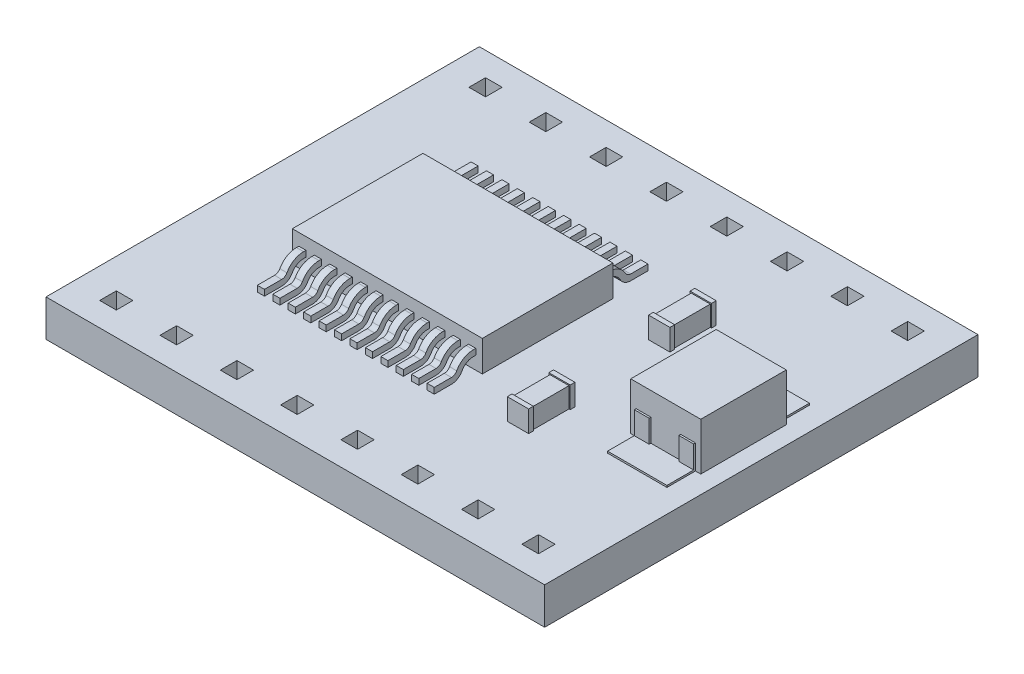
SolidWorks part; units mm, degrees
ref_plane "Спереди" through (0, 0, 0) normal (0, 0, 1) x (1, 0, 0)
ref_plane "Сверху" through (0, 0, 0) normal (0, 1, 0) x (1, 0, 0)
ref_plane "Справа" through (0, 0, 0) normal (1, 0, 0) x (0, 0, -1)
other "Configuration Table"
sketch "Эскиз1" plane through (0, 0, 0) normal (0, 1, 0) x (1, 0, 0)
  line L1 (-10.5, 9.125) -> (10.5, 9.125)
  line L2 (-10.5, 9.125) -> (-10.5, -9.125)
  line L3 (-10.5, -9.125) -> (10.5, -9.125)
  line L4 (10.5, 9.125) -> (10.5, -9.125)
  line L5 (0, -9.125) -> (0, 9.125) construction
  line L6 (-10.5, 0) -> (10.5, 0) construction
  point P0 (0, 0)
  dimension "D1" = 21
  dimension "D2" = 18.25
extrude "Бобышка-Вытянуть1" add sketch "Эскиз1" along normal blind 1.55
sketch "Эскиз2" plane through (0, 1.55, 0) normal (0, 1, 0) x (1, 0, 0)
  line L0 (0, -9.125) -> (0, 9.125) construction
  line L1 (10.5, 9.125) -> (-10.5, 9.125) construction
  line L2 (3.46, 8.125) -> (3.46, 7.425)
  line L3 (0.92, 8.125) -> (1.62, 8.125)
  line L4 (0.92, 8.125) -> (0.92, 7.425)
  line L5 (0.92, 7.425) -> (1.62, 7.425)
  line L6 (1.62, 8.125) -> (1.62, 7.425)
  line L7 (1.27, 7.425) -> (1.27, 8.125) construction
  line L8 (0.92, 7.775) -> (1.62, 7.775) construction
  line L9 (-1.62, 8.125) -> (-0.92, 8.125)
  line L10 (-1.62, 8.125) -> (-1.62, 7.425)
  line L11 (-1.62, 7.425) -> (-0.92, 7.425)
  line L12 (-0.92, 8.125) -> (-0.92, 7.425)
  line L13 (-1.27, 7.425) -> (-1.27, 8.125) construction
  line L14 (-1.62, 7.775) -> (-0.92, 7.775) construction
  line L15 (3.46, 8.125) -> (4.16, 8.125)
  line L16 (4.16, 8.125) -> (4.16, 7.425)
  line L17 (3.46, 7.425) -> (4.16, 7.425)
  line L18 (6, 8.125) -> (6, 7.425)
  line L19 (6, 8.125) -> (6.7, 8.125)
  line L20 (6.7, 8.125) -> (6.7, 7.425)
  line L21 (6, 7.425) -> (6.7, 7.425)
  line L22 (8.54, 8.125) -> (8.54, 7.425)
  line L23 (8.54, 8.125) -> (9.24, 8.125)
  line L24 (9.24, 8.125) -> (9.24, 7.425)
  line L25 (8.54, 7.425) -> (9.24, 7.425)
  line L26 (-8.54, 7.425) -> (-9.24, 7.425)
  line L27 (-9.24, 8.125) -> (-9.24, 7.425)
  line L28 (-8.54, 8.125) -> (-9.24, 8.125)
  line L29 (-8.54, 8.125) -> (-8.54, 7.425)
  line L30 (-6, 7.425) -> (-6.7, 7.425)
  line L31 (-6.7, 8.125) -> (-6.7, 7.425)
  line L32 (-6, 8.125) -> (-6.7, 8.125)
  line L33 (-6, 8.125) -> (-6, 7.425)
  line L34 (-3.46, 7.425) -> (-4.16, 7.425)
  line L35 (-4.16, 8.125) -> (-4.16, 7.425)
  line L36 (-3.46, 8.125) -> (-4.16, 8.125)
  line L37 (-3.46, 8.125) -> (-3.46, 7.425)
  line L38 (0, 0) -> (10.5, 0) construction
  line L39 (10.5, -9.125) -> (10.5, 9.125) construction
  line L40 (-1.62, -7.775) -> (-0.92, -7.775) construction
  line L41 (-1.27, -7.425) -> (-1.27, -8.125) construction
  line L42 (0.92, -7.775) -> (1.62, -7.775) construction
  line L43 (1.27, -7.425) -> (1.27, -8.125) construction
  line L44 (-3.46, -8.125) -> (-3.46, -7.425)
  line L45 (-3.46, -8.125) -> (-4.16, -8.125)
  line L46 (-4.16, -8.125) -> (-4.16, -7.425)
  line L47 (-3.46, -7.425) -> (-4.16, -7.425)
  line L48 (-6, -8.125) -> (-6, -7.425)
  line L49 (-6, -8.125) -> (-6.7, -8.125)
  line L50 (-6.7, -8.125) -> (-6.7, -7.425)
  line L51 (-6, -7.425) -> (-6.7, -7.425)
  line L52 (-8.54, -8.125) -> (-8.54, -7.425)
  line L53 (-8.54, -8.125) -> (-9.24, -8.125)
  line L54 (-9.24, -8.125) -> (-9.24, -7.425)
  line L55 (-8.54, -7.425) -> (-9.24, -7.425)
  line L56 (8.54, -7.425) -> (9.24, -7.425)
  line L57 (9.24, -8.125) -> (9.24, -7.425)
  line L58 (8.54, -8.125) -> (9.24, -8.125)
  line L59 (8.54, -8.125) -> (8.54, -7.425)
  line L60 (6, -7.425) -> (6.7, -7.425)
  line L61 (6.7, -8.125) -> (6.7, -7.425)
  line L62 (6, -8.125) -> (6.7, -8.125)
  line L63 (6, -8.125) -> (6, -7.425)
  line L64 (3.46, -7.425) -> (4.16, -7.425)
  line L65 (4.16, -8.125) -> (4.16, -7.425)
  line L66 (3.46, -8.125) -> (4.16, -8.125)
  line L67 (-0.92, -8.125) -> (-0.92, -7.425)
  line L68 (-1.62, -7.425) -> (-0.92, -7.425)
  line L69 (-1.62, -8.125) -> (-1.62, -7.425)
  line L70 (-1.62, -8.125) -> (-0.92, -8.125)
  line L71 (1.62, -8.125) -> (1.62, -7.425)
  line L72 (0.92, -7.425) -> (1.62, -7.425)
  line L73 (0.92, -8.125) -> (0.92, -7.425)
  line L74 (0.92, -8.125) -> (1.62, -8.125)
  line L75 (3.46, -8.125) -> (3.46, -7.425)
  line L76 (-9.24, 7.775) -> (-8.54, 7.775) construction
  point P5 (1.27, 7.775)
  point P9 (-1.27, 7.775)
  point P86 (-1.27, -7.775)
  point P87 (1.27, -7.775)
  dimension "D1" = 0.7
  dimension "D2" = 2.54
  dimension "D4" = 2.54
  dimension "D5" = 1.35
  dimension "D6" = 0.7
  dimension "D3" = 4
extrude "Вырез-Вытянуть1" cut sketch "Эскиз2" against normal through all
sketch "Эскиз3" plane through (0, 1.55, 0) normal (0, 1, 0) x (1, 0, 0)
  line L0 (-10.5, 9.125) -> (-10.5, -9.125) construction
  line L1 (-6.5, 2.75) -> (1.5, 2.75)
  line L2 (-6.5, 2.75) -> (-6.5, -2.75)
  line L3 (-6.5, -2.75) -> (1.5, -2.75)
  line L4 (1.5, 2.75) -> (1.5, -2.75)
  line L5 (-2.5, -2.75) -> (-2.5, 2.75) construction
  line L6 (-6.5, 0) -> (1.5, 0) construction
  point P0 (-2.5, 0)
  dimension "D1" = 8
  dimension "D2" = 5.5
  dimension "D3" = 4
extrude "Бобышка-Вытянуть2" add sketch "Эскиз3" along normal blind 1.3
sketch "Эскиз4" plane through (0, 1.55, 0) normal (0, 1, 0) x (1, 0, 0)
  line L0 (-2.5, -2.75) -> (-2.5, 2.75) construction
  line L1 (-6.5, -2.75) -> (1.5, -2.75) construction
  line L2 (1.5, 2.75) -> (-6.5, 2.75) construction
  line L3 (-2.325, -2.75) -> (-2.325, -4.5)
  line L4 (-2.325, -4.5) -> (-2.025, -4.5)
  line L5 (-2.025, -4.5) -> (-2.025, -2.75)
  line L6 (-6.5, -2.75) -> (1.5, -2.75) construction
  line L7 (-6.5, 0) -> (1.5, 0) construction
  line L8 (-6.5, 2.75) -> (-6.5, -2.75) construction
  line L9 (1.5, -2.75) -> (1.5, 2.75) construction
  line L10 (-2.325, -2.75) -> (-2.025, -2.75)
  line L11 (-2.325, 2.75) -> (-2.025, 2.75)
  line L12 (-2.025, 4.5) -> (-2.025, 2.75)
  line L13 (-2.325, 4.5) -> (-2.025, 4.5)
  line L14 (-2.325, 2.75) -> (-2.325, 4.5)
  line L15 (-1.675, -2.75) -> (-1.675, -4.5)
  line L16 (-1.675, -4.5) -> (-1.375, -4.5)
  line L17 (-1.375, -4.5) -> (-1.375, -2.75)
  line L18 (-1.675, -2.75) -> (-1.375, -2.75)
  line L19 (-1.675, 2.75) -> (-1.375, 2.75)
  line L20 (-1.375, 4.5) -> (-1.375, 2.75)
  line L21 (-1.675, 4.5) -> (-1.375, 4.5)
  line L22 (-1.675, 2.75) -> (-1.675, 4.5)
  line L23 (-1.025, -2.75) -> (-1.025, -4.5)
  line L24 (-1.025, -4.5) -> (-0.725, -4.5)
  line L25 (-0.725, -4.5) -> (-0.725, -2.75)
  line L26 (-1.025, -2.75) -> (-0.725, -2.75)
  line L27 (-1.025, 2.75) -> (-0.725, 2.75)
  line L28 (-0.725, 4.5) -> (-0.725, 2.75)
  line L29 (-1.025, 4.5) -> (-0.725, 4.5)
  line L30 (-1.025, 2.75) -> (-1.025, 4.5)
  line L31 (-0.375, -2.75) -> (-0.375, -4.5)
  line L32 (-0.375, -4.5) -> (-0.075, -4.5)
  line L33 (-0.075, -4.5) -> (-0.075, -2.75)
  line L34 (-0.375, -2.75) -> (-0.075, -2.75)
  line L35 (-0.375, 2.75) -> (-0.075, 2.75)
  line L36 (-0.075, 4.5) -> (-0.075, 2.75)
  line L37 (-0.375, 4.5) -> (-0.075, 4.5)
  line L38 (-0.375, 2.75) -> (-0.375, 4.5)
  line L39 (0.275, -2.75) -> (0.275, -4.5)
  line L40 (0.275, -4.5) -> (0.575, -4.5)
  line L41 (0.575, -4.5) -> (0.575, -2.75)
  line L42 (0.275, -2.75) -> (0.575, -2.75)
  line L43 (0.275, 2.75) -> (0.575, 2.75)
  line L44 (0.575, 4.5) -> (0.575, 2.75)
  line L45 (0.275, 4.5) -> (0.575, 4.5)
  line L46 (0.275, 2.75) -> (0.275, 4.5)
  line L47 (0.925, -2.75) -> (0.925, -4.5)
  line L48 (0.925, -4.5) -> (1.225, -4.5)
  line L49 (1.225, -4.5) -> (1.225, -2.75)
  line L50 (0.925, -2.75) -> (1.225, -2.75)
  line L51 (0.925, 2.75) -> (1.225, 2.75)
  line L52 (1.225, 4.5) -> (1.225, 2.75)
  line L53 (0.925, 4.5) -> (1.225, 4.5)
  line L54 (0.925, 2.75) -> (0.925, 4.5)
  line L55 (-2.325, -2.75) -> (-1.675, -2.75) construction
  line L56 (-2.675, -2.75) -> (-3.325, -2.75) construction
  line L57 (-5.925, 2.75) -> (-5.925, 4.5)
  line L58 (-5.925, 4.5) -> (-6.225, 4.5)
  line L59 (-6.225, 4.5) -> (-6.225, 2.75)
  line L60 (-5.925, 2.75) -> (-6.225, 2.75)
  line L61 (-5.925, -2.75) -> (-6.225, -2.75)
  line L62 (-6.225, -4.5) -> (-6.225, -2.75)
  line L63 (-5.925, -4.5) -> (-6.225, -4.5)
  line L64 (-5.925, -2.75) -> (-5.925, -4.5)
  line L65 (-5.275, 2.75) -> (-5.275, 4.5)
  line L66 (-5.275, 4.5) -> (-5.575, 4.5)
  line L67 (-5.575, 4.5) -> (-5.575, 2.75)
  line L68 (-5.275, 2.75) -> (-5.575, 2.75)
  line L69 (-5.275, -2.75) -> (-5.575, -2.75)
  line L70 (-5.575, -4.5) -> (-5.575, -2.75)
  line L71 (-5.275, -4.5) -> (-5.575, -4.5)
  line L72 (-5.275, -2.75) -> (-5.275, -4.5)
  line L73 (-4.625, 2.75) -> (-4.625, 4.5)
  line L74 (-4.625, 4.5) -> (-4.925, 4.5)
  line L75 (-4.925, 4.5) -> (-4.925, 2.75)
  line L76 (-4.625, 2.75) -> (-4.925, 2.75)
  line L77 (-4.625, -2.75) -> (-4.925, -2.75)
  line L78 (-4.925, -4.5) -> (-4.925, -2.75)
  line L79 (-4.625, -4.5) -> (-4.925, -4.5)
  line L80 (-4.625, -2.75) -> (-4.625, -4.5)
  line L81 (-3.975, 2.75) -> (-3.975, 4.5)
  line L82 (-3.975, 4.5) -> (-4.275, 4.5)
  line L83 (-4.275, 4.5) -> (-4.275, 2.75)
  line L84 (-3.975, 2.75) -> (-4.275, 2.75)
  line L85 (-3.975, -2.75) -> (-4.275, -2.75)
  line L86 (-4.275, -4.5) -> (-4.275, -2.75)
  line L87 (-3.975, -4.5) -> (-4.275, -4.5)
  line L88 (-3.975, -2.75) -> (-3.975, -4.5)
  line L89 (-3.325, 2.75) -> (-3.325, 4.5)
  line L90 (-3.325, 4.5) -> (-3.625, 4.5)
  line L91 (-3.625, 4.5) -> (-3.625, 2.75)
  line L92 (-3.325, 2.75) -> (-3.625, 2.75)
  line L93 (-3.325, -2.75) -> (-3.625, -2.75)
  line L94 (-3.625, -4.5) -> (-3.625, -2.75)
  line L95 (-3.325, -4.5) -> (-3.625, -4.5)
  line L96 (-3.325, -2.75) -> (-3.325, -4.5)
  line L97 (-2.675, 2.75) -> (-2.675, 4.5)
  line L98 (-2.675, 4.5) -> (-2.975, 4.5)
  line L99 (-2.975, 4.5) -> (-2.975, 2.75)
  line L100 (-2.675, 2.75) -> (-2.975, 2.75)
  line L101 (-2.675, -2.75) -> (-2.975, -2.75)
  line L102 (-2.975, -4.5) -> (-2.975, -2.75)
  line L103 (-2.675, -4.5) -> (-2.975, -4.5)
  line L104 (-2.675, -2.75) -> (-2.675, -4.5)
  dimension "D1" = 9
  dimension "D3" = 0.35
  dimension "D4" = 0.3
  dimension "D5" = 0.35
  dimension "D2" = 6
extrude "Бобышка-Вытянуть4" add sketch "Эскиз4" along normal offset from surface (0.8 mm away) 0.5 up to face at (-2.5, 2.85, 0)
sketch "Эскиз5" plane through (-6.5, 0, 0) normal (-1, 0, 0) x (0, 0, 1)
  line L1 (2.75, 1.55) -> (4.5, 1.55) construction
  line L2 (2.75, 1.55) -> (3.7733, 1.55)
  line L3 (2.75, 2.35) -> (4.5, 2.35) construction
  line L4 (-9.125, 1.55) -> (9.125, 1.55) construction
  line L5 (3.7733, 1.55) -> (4.5, 1.55)
  line L6 (4.5, 1.55) -> (4.5, 1.8)
  line L7 (4.5, 2.35) -> (4.5, 1.55) construction
  line L8 (4.5, 1.8) -> (3.7733, 1.8)
  line L9 (2.75, 1.55) -> (2.75, 2.1)
  line L10 (2.75, 2.85) -> (2.75, 1.55) construction
  line L11 (2.75, 2.1) -> (2.85, 2.1)
  line L12 (2.75, 2.35) -> (2.85, 2.35)
  line L13 (4.5, 1.8) -> (4.5, 2.35)
  line L14 (4.5, 2.35) -> (2.85, 2.35)
  line L15 (0, 2.85) -> (0, 1.55) construction
  line L16 (-2.75, 2.85) -> (2.75, 2.85) construction
  line L17 (-4.5, 1.8) -> (-3.7733, 1.8)
  line L18 (-4.5, 2.35) -> (-2.85, 2.35)
  line L19 (-4.5, 1.8) -> (-4.5, 2.35)
  line L20 (-2.75, 1.55) -> (-3.7733, 1.55)
  line L21 (-2.75, 2.1) -> (-2.85, 2.1)
  line L22 (-2.75, 1.55) -> (-2.75, 2.1)
  arc A1 (3.3336, 1.8119) -> (2.85, 2.1) centre (2.85, 1.55) ccw
  arc A2 (3.3336, 1.8119) -> (3.7733, 1.55) centre (3.7733, 2.05) ccw
  arc A3 (2.85, 2.35) -> (3.5535, 1.931) centre (2.85, 1.55) cw
  arc A4 (3.7733, 1.8) -> (3.5535, 1.931) centre (3.7733, 2.05) cw
  arc A5 (-2.85, 2.35) -> (-3.5535, 1.931) centre (-2.85, 1.55) ccw
  arc A6 (-3.7733, 1.8) -> (-3.5535, 1.931) centre (-3.7733, 2.05) ccw
  arc A7 (-3.3336, 1.8119) -> (-2.85, 2.1) centre (-2.85, 1.55) cw
  arc A8 (-3.3336, 1.8119) -> (-3.7733, 1.55) centre (-3.7733, 2.05) cw
  point P3 (3.6454, 1.8352)
  point P38 (3.5174, 1.6204)
  line M10 (2.75, 1.55) -> (2.75, 2.85)
  line M12 (-2.75, 2.85) -> (-2.75, 1.55)
  dimension "D5" = 0.25
  dimension "D1" = 0.25
  dimension "D2" = 0.25
  dimension "D3" = 0.1
  dimension "D4" = 0.25
extrude "Вырез-Вытянуть2" cut sketch "Эскиз5" against normal through all contours A7 A8 L20 L21 M12 | L17 A6 A5 L18 L19 | A2 A1 L11 L2 M10 | A4 L8 L13 L14 A3 region at (-6.5, 1.7788, 3.0608) region at (-6.5, 2.1008, 3.9418) region at (-6.5, 2.1008, -3.9418) region at (-6.5, 1.7788, -3.0608)
sketch "Эскиз6" plane through (0, 1.55, 0) normal (0, 1, 0) x (1, 0, 0)
  line L0 (10.5, -9.125) -> (10.5, 9.125) construction
  line L1 (9.75, 1.8) -> (6.8, 1.8)
  line L2 (9.75, 1.8) -> (9.75, -1.8)
  line L3 (9.75, -1.8) -> (6.8, -1.8)
  line L4 (6.8, 1.8) -> (6.8, -1.8)
  line L5 (8.275, -1.8) -> (8.275, 1.8) construction
  line L6 (9.75, 0) -> (6.8, 0) construction
  point P0 (8.275, 0)
  dimension "D1" = 3.6
  dimension "D2" = 2.95
  dimension "D3" = 0.75
extrude "Бобышка-Вытянуть5" add sketch "Эскиз6" along normal offset from surface (2 mm away) 3.55 up to face at (8.89, 0, -7.775)
sketch "Эскиз7" plane through (0, 1.55, 0) normal (0, 1, 0) x (1, 0, 0)
  line L0 (7.025, 1.8) -> (7.025, 3)
  line L1 (9.75, 1.8) -> (6.8, 1.8) construction
  line L2 (7.025, 3) -> (9.525, 3)
  line L3 (9.525, 3) -> (9.525, 1.8)
  line L4 (9.75, 1.8) -> (6.8, 1.8) construction
  line L5 (9.525, 1.8) -> (7.025, 1.8)
  line L6 (9.525, -1.8) -> (7.025, -1.8)
  line L9 (6.8, 0) -> (9.75, 0) construction
  line L10 (6.8, 1.8) -> (6.8, -1.8) construction
  line L11 (9.75, -1.8) -> (9.75, 1.8) construction
  line L12 (9.525, -3) -> (9.525, -1.8)
  line L13 (7.025, -3) -> (9.525, -3)
  line L14 (7.025, -1.8) -> (7.025, -3)
  line L15 (8.275, 1.8) -> (8.275, -3) construction
  dimension "D1" = 6
  dimension "D2" = 2.5
extrude "Бобышка-Вытянуть6" add sketch "Эскиз7" along normal blind 0.075
sketch "Эскиз8" plane through (0, 0, -1.8) normal (0, 0, -1) x (-1, 0, 0)
  line L0 (-9.525, 1.625) -> (-9.525, 2.575)
  line L1 (-9.525, 2.575) -> (-8.9, 2.575)
  line L2 (-8.9, 2.575) -> (-8.9, 1.625)
  line L3 (-9.525, 1.625) -> (-7.025, 1.625) construction
  line L4 (-8.9, 1.625) -> (-9.525, 1.625)
  line L5 (-8.275, 3.55) -> (-8.275, 1.625) construction
  line L6 (-9.75, 3.55) -> (-6.8, 3.55) construction
  line L7 (-7.025, 1.625) -> (-9.525, 1.625) construction
  line L8 (-7.65, 1.625) -> (-7.025, 1.625)
  line L9 (-7.65, 2.575) -> (-7.65, 1.625)
  line L10 (-7.025, 2.575) -> (-7.65, 2.575)
  line L11 (-7.025, 1.625) -> (-7.025, 2.575)
  dimension "D1" = 1.25
  dimension "D2" = 0.95
extrude "Бобышка-Вытянуть7" add sketch "Эскиз8" along normal blind 0.075
mirror "Зеркальное отражение1" about plane through (0, 0, 0) normal (0, 0, 1) of "Бобышка-Вытянуть7"
sketch "Эскиз9" plane through (0, 1.55, 0) normal (0, 1, 0) x (1, 0, 0)
  line L0 (10.5, -9.125) -> (10.5, 9.125) construction
  line L1 (3.8, 3.85) -> (4.6, 3.85)
  line L2 (3.8, 3.85) -> (3.8, 2.1)
  line L3 (3.8, 2.1) -> (4.6, 2.1)
  line L4 (4.6, 3.85) -> (4.6, 2.1)
  line L5 (4.2, 2.1) -> (4.2, 3.85) construction
  line L6 (3.8, 2.975) -> (4.6, 2.975) construction
  line L7 (10.5, 0) -> (-10.5, 0) construction
  line L8 (-10.5, 9.125) -> (-10.5, -9.125) construction
  line L9 (3.8, -2.975) -> (4.6, -2.975) construction
  line L10 (4.2, -2.1) -> (4.2, -3.85) construction
  line L11 (4.6, -3.85) -> (4.6, -2.1)
  line L12 (3.8, -2.1) -> (4.6, -2.1)
  line L13 (3.8, -3.85) -> (3.8, -2.1)
  line L14 (3.8, -3.85) -> (4.6, -3.85)
  point P0 (4.2, 2.975)
  point P18 (4.2, -2.975)
  dimension "D1" = 1.75
  dimension "D2" = 0.8
  dimension "D3" = 5.9
  dimension "D4" = 4.2
extrude "Бобышка-Вытянуть8" add sketch "Эскиз9" along normal offset from surface (0.85 mm away) 2.4 up to face at (8.89, 0, -7.775)
sketch "Эскиз10" plane through (0, 2.4, 0) normal (0, 1, 0) x (1, 0, 0)
  line L0 (4.6, -2.1) -> (3.8, -2.1) construction
  line L1 (3.75, -2) -> (4.65, -2)
  line L2 (3.75, -2) -> (3.75, -2.2)
  line L3 (3.75, -2.2) -> (4.65, -2.2)
  line L4 (4.65, -2) -> (4.65, -2.2)
  line L5 (4.2, -2.2) -> (4.2, -2) construction
  line L6 (3.75, -2.1) -> (4.65, -2.1) construction
  line L7 (3.8, -2.975) -> (4.6, -2.975) construction
  line L8 (3.8, -2.1) -> (3.8, -3.85) construction
  line L9 (4.6, -3.85) -> (4.6, -2.1) construction
  line L10 (3.75, -3.85) -> (4.65, -3.85) construction
  line L11 (4.2, -3.75) -> (4.2, -3.95) construction
  line L12 (4.65, -3.95) -> (4.65, -3.75)
  line L13 (3.75, -3.75) -> (4.65, -3.75)
  line L14 (3.75, -3.95) -> (3.75, -3.75)
  line L15 (3.75, -3.95) -> (4.65, -3.95)
  line L16 (-50, 0) -> (50, 0) construction
  line L17 (4.2, 3.75) -> (4.2, 3.95) construction
  line L18 (3.75, 3.85) -> (4.65, 3.85) construction
  line L19 (3.8, 2.975) -> (4.6, 2.975) construction
  line L20 (3.75, 2.1) -> (4.65, 2.1) construction
  line L21 (4.2, 2.2) -> (4.2, 2) construction
  line L22 (3.75, 3.95) -> (4.65, 3.95)
  line L23 (3.75, 3.95) -> (3.75, 3.75)
  line L24 (3.75, 3.75) -> (4.65, 3.75)
  line L25 (4.65, 3.95) -> (4.65, 3.75)
  line L26 (4.65, 2) -> (4.65, 2.2)
  line L27 (3.75, 2.2) -> (4.65, 2.2)
  line L28 (3.75, 2) -> (3.75, 2.2)
  line L29 (3.75, 2) -> (4.65, 2)
  point P0 (4.2, -2.1)
  point P20 (4.2, -3.85)
  point P41 (4.2, 3.85)
  point P42 (4.2, 2.1)
  dimension "D1" = 0.1
  dimension "D2" = 0.05
extrude "Бобышка-Вытянуть9" add sketch "Эскиз10" against normal blind 2.4 and the other way blind 0.05
ref_plane "Плоскость1" through (8.89, 0, 0) normal (1, 0, 0) x (0, 0, -1)
sketch "Эскиз11" plane through (8.89, 0, 0) normal (1, 0, 0) x (0, 0, -1)
  line L0 (7.775, 1.55) -> (7.775, 0) construction
  line L1 (7.425, 1.55) -> (8.125, 1.55) construction
  line L2 (7.425, 0) -> (8.125, 0) construction
  line L3 (7.775, 3.05) -> (7.275, 3.05)
  line L4 (6.955, 1.55) -> (6.955, 1.6)
  line L5 (-9.125, 1.55) -> (9.125, 1.55) construction
  line L6 (7.775, 3.05) -> (7.775, 1.55)
  line L7 (7.775, 1.55) -> (6.955, 1.55)
  line L9 (9.125, 0.775) -> (-9.125, 0.775) construction
  line L10 (9.125, 1.55) -> (9.125, 0) construction
  line L11 (-9.125, 1.55) -> (-9.125, 0) construction
  line L12 (7.775, 0) -> (6.955, 0)
  line L13 (7.775, -1.5) -> (7.775, 0)
  line L14 (6.955, 0) -> (6.955, -0.05)
  line L15 (7.775, -1.5) -> (7.275, -1.5)
  arc A0 (7.275, 3.05) -> (7.0479, 2.0209) centre (4.8298, 3.05) cw
  arc A1 (6.955, 1.6) -> (7.0479, 2.0209) centre (7.955, 1.6) cw
  arc A2 (6.955, -0.05) -> (7.0479, -0.4709) centre (7.955, -0.05) ccw
  arc A3 (7.275, -1.5) -> (7.0479, -0.4709) centre (4.8298, -1.5) ccw
  dimension "D5" = 1
  dimension "D1" = 1.5
  dimension "D2" = 0.82
  dimension "D3" = 0.05
  dimension "D4" = 0.5
revolve "Повернуть1" [suppressed] add sketch "Эскиз11" angle 360 about L0
fillet "Скругление1" [suppressed] radius 0.1
fillet "Скругление2" [suppressed] radius 0.15
pattern_linear "Линейный массив1" [suppressed] count 8 spacing 2.54 of bodies 115
mirror "Зеркальное отражение2" [suppressed] about plane through (0, 0, 0) normal (0, 0, 1)
